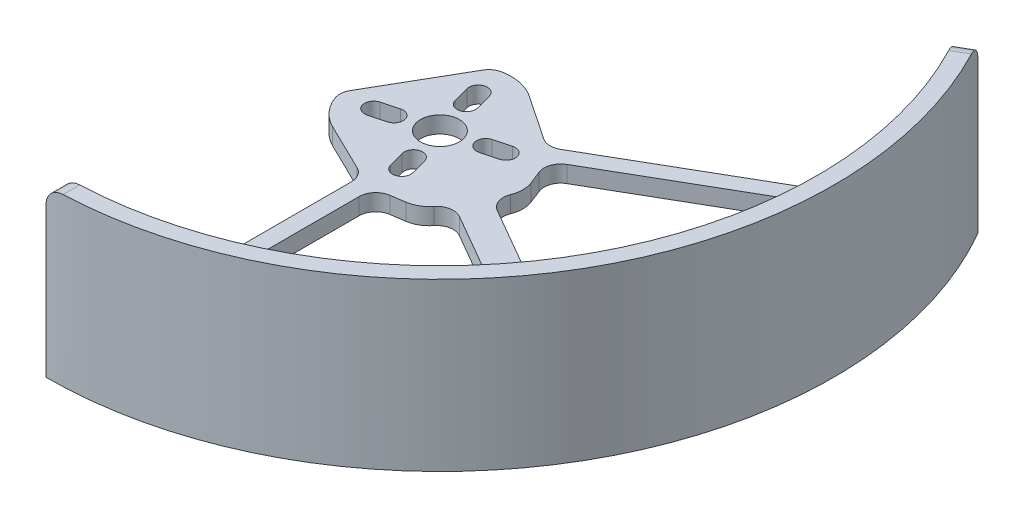
SolidWorks part; units mm, degrees
material "ABS"
ref_plane "Front Plane" through (0, 0, 0) normal (0, 0, 1) x (1, 0, 0)
ref_plane "Top Plane" through (0, 0, 0) normal (0, 1, 0) x (1, 0, 0)
ref_plane "Right Plane" through (0, 0, 0) normal (1, 0, 0) x (0, 0, -1)
sketch "Sketch1" plane through (0, 0, 0) normal (0, 1, 0) x (1, 0, 0)
  line L0 (0, 0) -> (0, -71) construction
  line L1 (0, 0) -> (61.4878, 35.5) construction
  line L2 (0, -68) -> (0, -71)
  line L3 (58.8897, 34) -> (61.4878, 35.5)
  arc A0 (0, -68) -> (58.8897, 34) centre (0, 0) ccw
  arc A1 (0, -71) -> (61.4878, 35.5) centre (0, 0) ccw
  dimension "D1" = 136
  dimension "D2" = 142
  dimension "D3" = 120
extrude "Boss-Extrude1" add sketch "Sketch1" along normal blind 30
sketch "Sketch4" plane through (0, 0, 0) normal (0, -1, 0) x (1, 0, 0)
  line L0 (2.673, -13.4439) -> (12.8584, -6.5738) construction
  line L1 (14.7145, -4.2611) -> (16.3536, -0.1001) construction
  line L3 (8.0901, 14.2127) -> (3.667, 14.8737) construction
  line L5 (2.673, -13.4439) -> (12.1794, -7.0318)
  line L6 (14.7145, -4.2611) -> (16.3536, -0.1001)
  line L7 (11.6812, 11.7676) -> (16.0316, 4.2324) construction
  line L8 (8.0901, 14.2127) -> (3.667, 14.8737)
  line L9 (0, 14.0636) -> (-10.3063, 9.0369)
  line L10 (58.8897, -34) -> (12.1794, -7.0318)
  line L11 (61.4878, -35.5) -> (58.8897, -34) construction
  line L12 (60.3324, -31.3688) -> (14.4281, -4.866)
  line L13 (16.0316, 4.2324) -> (60.9443, 30.1628) construction
  line L14 (11.6812, 11.7676) -> (56.5939, 37.6979) construction
  line L15 (0, 68) -> (0, 14.0636)
  line L16 (3, 14.9281) -> (3, 67.9338)
  line L17 (60.0193, 31.7649) -> (57.5193, 36.095) construction
  line L18 (61.4878, 35.5) -> (57.7678, 33.3523) construction
  line L19 (9.4178, -2.5235) -> (6.52, -1.747) construction
  line L20 (8.9907, -4.1173) -> (6.0929, -3.3408)
  line L21 (9.8448, -0.9297) -> (6.9471, -0.1533)
  line L22 (2.5235, 9.4178) -> (1.747, 6.52) construction
  line L23 (4.1173, 8.9907) -> (3.3408, 6.0929)
  line L24 (0.9297, 9.8448) -> (0.1533, 6.9471)
  line L25 (-6.52, 1.747) -> (-9.4178, 2.5235) construction
  line L26 (-6.9471, 0.1533) -> (-9.8448, 0.9297)
  line L27 (-6.0929, 3.3408) -> (-8.9907, 4.1173)
  line L28 (-2.5235, -9.4178) -> (-1.747, -6.52) construction
  line L29 (-4.1173, -8.9907) -> (-3.3408, -6.0929)
  line L30 (-0.9297, -9.8448) -> (-0.1533, -6.9471)
  line L31 (-4.988, -14.3843) -> (-14.9511, 2.8724)
  line L32 (12.6066, 10.1647) -> (57.6001, 36.1417)
  line L33 (15.1066, 5.8346) -> (60.1001, 31.8116)
  line L34 (16.0316, 4.2324) -> (15.1066, 5.8346)
  line L35 (11.6812, 11.7676) -> (12.6066, 10.1647)
  arc A0 (-4.988, -14.3843) -> (2.673, -13.4439) centre (-2.0801, -6.3971) ccw construction
  arc A1 (12.8584, -6.5738) -> (14.7145, -4.2611) centre (10.0624, -2.4286) ccw construction
  arc A2 (16.3536, -0.1001) -> (16.0316, 4.2324) centre (11.7015, 1.7324) ccw construction
  arc A3 (11.6812, 11.7676) -> (8.0901, 14.2127) centre (7.3511, 9.2676) ccw construction
  arc A5 (-10.3063, 9.0369) -> (-14.9511, 2.8724) centre (-6.5801, 1.3971) ccw construction
  arc A6 (-4.988, -14.3843) -> (2.673, -13.4439) centre (-2.0801, -6.3971) ccw
  arc A7 (14.4281, -4.866) -> (14.7145, -4.2611) centre (10.0624, -2.4286) ccw
  arc A8 (16.3536, -0.1001) -> (16.0316, 4.2324) centre (11.7015, 1.7324) ccw
  arc A9 (11.6812, 11.7676) -> (8.0901, 14.2127) centre (7.3511, 9.2676) ccw
  arc A10 (3.667, 14.8737) -> (3, 14.9281) centre (2.928, 9.9286) ccw
  arc A11 (-10.3063, 9.0369) -> (-14.9511, 2.8724) centre (-6.5801, 1.3971) ccw
  arc A12 (61.4878, -35.5) -> (0, 71) centre (0, 0) ccw construction
  arc A14 (58.8897, -34) -> (60.3324, -31.3688) centre (0, 0) ccw
  arc A15 (8.9907, -4.1173) -> (9.8448, -0.9297) centre (9.4178, -2.5235) ccw
  arc A16 (6.9471, -0.1533) -> (6.0929, -3.3408) centre (6.52, -1.747) ccw
  arc A17 (4.1173, 8.9907) -> (0.9297, 9.8448) centre (2.5235, 9.4178) ccw
  arc A18 (0.1533, 6.9471) -> (3.3408, 6.0929) centre (1.747, 6.52) ccw
  arc A19 (-6.9471, 0.1533) -> (-6.0929, 3.3408) centre (-6.52, 1.747) ccw
  arc A20 (-8.9907, 4.1173) -> (-9.8448, 0.9297) centre (-9.4178, 2.5235) ccw
  arc A21 (-4.1173, -8.9907) -> (-0.9297, -9.8448) centre (-2.5235, -9.4178) ccw
  arc A22 (-0.1533, -6.9471) -> (-3.3408, -6.0929) centre (-1.747, -6.52) ccw
  circle A23 centre (0, 0) radius 3.5
  arc A24 (60.1001, 31.8116) -> (57.6001, 36.1417) centre (0, 0) ccw
  arc A25 (3, 67.9338) -> (0, 68) centre (0, 0) ccw
  arc A26 (58.8897, -34) -> (0, 68) centre (0, 0) ccw construction
  point P22 (58.8897, -34)
  point P46 (7.9689, -2.1353)
  point P51 (2.1353, 7.9689)
  point P60 (-7.9689, 2.1353)
  point P69 (-2.1353, -7.9689)
  point P83 (60.3324, -31.3688)
  point P88 (3, 67.9338)
  dimension "D3" = 1.65
  dimension "D4" = 7
  dimension "D5" = 5
  dimension "D1" = 3
  dimension "D2" = 3
  dimension "D6" = 1.85
extrude "Boss-Extrude2" add sketch "Sketch4" against normal blind 3
fillet "Fillet3" radius 3 14 edges at (0, 30, 69.5) (60.1888, 30, -34.75) (60.3324, 1.5, -31.3688) (14.4281, 1.5, -4.866) (15.1066, 1.5, 5.8346) (60.1001, 1.5, 31.8116) (57.6001, 1.5, 36.1417) (12.6066, 1.5, 10.1647) (3, 1.5, 14.9281) (3, 1.5, 67.9338) (0, 1.5, 14.0636) (-14.9511, 1.5, 2.8724) (-4.988, 1.5, -14.3843) (12.1794, 1.5, -7.0318)
chamfer "Chamfer1" distance 2 angle 45 3 edges at (60.3977, 3, -31.2428) (3.1418, 3, 67.9274) (58.89, 3, 33.9996)
